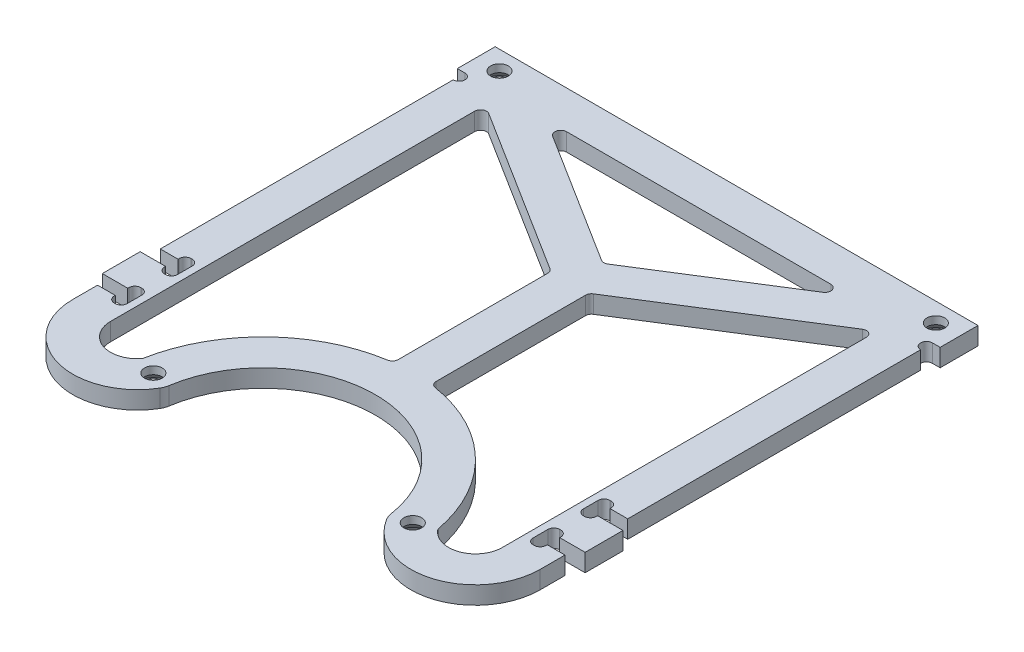
SolidWorks part; units mm, degrees
ref_plane "Front Plane" through (0, 0, 0) normal (0, 0, 1) x (1, 0, 0)
ref_plane "Top Plane" through (0, 0, 0) normal (0, 1, 0) x (1, 0, 0)
ref_plane "Right Plane" through (0, 0, 0) normal (1, 0, 0) x (0, 0, -1)
sketch "Sketch1" plane through (0, 0, 0) normal (0, 1, 0) x (1, 0, 0)
  line L0 (-36.88, 36.725) -> (36.88, 36.725) construction
  line L1 (36.88, 36.725) -> (21.92, -36.725) construction
  line L2 (21.92, -36.725) -> (-21.92, -36.725) construction
  line L3 (-21.92, -36.725) -> (-36.88, 36.725) construction
  line L4 (0, -40.095) -> (0, -36.725) construction
  line L5 (0, 36.725) -> (0, -36.725) construction
  line L6 (-39.5, -13.775) -> (-39.5, 33.525)
  line L7 (-33.1, -13.775) -> (-33.1, 33.525)
  line L8 (-39.5, 9.875) -> (-33.1, 9.875) construction
  line L9 (0, 33.525) -> (0, 39.925) construction
  line L10 (-39.5, -23.275) -> (-33.1, -23.275) construction
  line L13 (40.8, 33.525) -> (-40.8, 33.525)
  line L14 (40.8, 33.525) -> (40.8, 39.925)
  line L15 (40.8, 39.925) -> (-40.8, 39.925)
  line L16 (-40.8, 33.525) -> (-40.8, 39.925)
  line L17 (40.8, 33.525) -> (-40.8, 39.925) construction
  line L18 (40.8, 39.925) -> (-40.8, 33.525) construction
  line L19 (39.5, 33.525) -> (-39.5, 33.525)
  line L20 (39.5, 33.525) -> (39.5, 39.925)
  line L21 (39.5, 39.925) -> (-39.5, 39.925)
  line L22 (-39.5, 33.525) -> (-39.5, 39.925)
  line L23 (39.5, 33.525) -> (-39.5, 39.925) construction
  line L24 (39.5, 39.925) -> (-39.5, 33.525) construction
  line L27 (-34.3, -25.275) -> (-36.5, -25.275)
  line L28 (-39.5, -20.075) -> (-40.8, -20.075)
  line L29 (-34.3, -16.775) -> (-34.3, -13.775) construction
  line L30 (-33.1, -32.775) -> (-39.5, -32.775)
  line L31 (-33.1, -32.775) -> (-33.1, -13.775)
  line L32 (-33.1, -13.775) -> (-39.5, -13.775)
  line L33 (-39.5, -32.775) -> (-39.5, -13.775)
  line L34 (-33.1, -32.775) -> (-39.5, -13.775) construction
  line L35 (-33.1, -13.775) -> (-39.5, -32.775) construction
  line L36 (-39.5, -20.075) -> (-36.5, -20.075)
  line L37 (-39.5, -20.075) -> (-39.5, -17.975)
  line L38 (-39.5, -17.975) -> (-36.5, -17.975)
  line L39 (-36.5, -20.075) -> (-36.5, -17.975)
  line L40 (-36.5, -19.025) -> (-39.5, -19.025) construction
  line L41 (-36.5, -19.025) -> (-33.1, -19.025) construction
  line L42 (-35.4, -32.775) -> (-35.4, -13.775) construction
  line L43 (-34.3, -21.275) -> (-36.5, -21.275)
  line L44 (-34.3, -21.275) -> (-34.3, -16.775)
  line L45 (-34.3, -16.775) -> (-36.5, -16.775)
  line L46 (-36.5, -21.275) -> (-36.5, -16.775)
  line L47 (-34.3, -21.275) -> (-36.5, -16.775) construction
  line L48 (-34.3, -16.775) -> (-36.5, -21.275) construction
  line L53 (-34.3, -25.275) -> (-34.3, -29.775)
  line L58 (-34.3, -29.775) -> (-36.5, -29.775)
  line L67 (39.5, -17.975) -> (36.5, -17.975)
  line L68 (-36.5, -25.275) -> (-36.5, -29.775)
  line L69 (-39.5, -28.575) -> (-36.5, -28.575)
  line L70 (-39.5, -20.075) -> (-39.5, -26.475)
  line L71 (-39.5, -26.475) -> (-40.8, -26.475)
  line L72 (-40.8, -20.075) -> (-40.8, -26.475)
  line L73 (-39.5, -20.075) -> (-40.8, -26.475) construction
  line L74 (-39.5, -26.475) -> (-40.8, -20.075) construction
  line L75 (-39.5, -26.475) -> (-36.5, -26.475)
  line L76 (39.5, -20.075) -> (36.5, -20.075)
  line L77 (39.5, -28.575) -> (36.5, -28.575)
  line L78 (39.5, -26.475) -> (36.5, -26.475)
  line L79 (36.5, -25.275) -> (36.5, -29.775)
  line L80 (34.3, -29.775) -> (36.5, -29.775)
  line L81 (34.3, -25.275) -> (34.3, -29.775)
  line L82 (34.3, -25.275) -> (36.5, -25.275)
  line L83 (34.3, -21.275) -> (36.5, -21.275)
  line L84 (34.3, -21.275) -> (34.3, -16.775)
  line L85 (34.3, -16.775) -> (36.5, -16.775)
  line L86 (36.5, -21.275) -> (36.5, -16.775)
  line L87 (39.5, -17.975) -> (36.5, -17.975)
  line L88 (39.5, -20.075) -> (40.8, -20.075)
  line L89 (40.8, -20.075) -> (40.8, -26.475)
  line L90 (39.5, -26.475) -> (40.8, -26.475)
  line L91 (39.5, -32.775) -> (39.5, -13.775)
  line L92 (33.1, -32.775) -> (33.1, -13.775)
  line L93 (33.1, -13.775) -> (33.1, 33.525)
  line L94 (39.5, -13.775) -> (39.5, 33.525)
  line L95 (-36.88, 36.725) -> (0, 13.525) construction
  line L96 (0, 13.525) -> (36.88, 36.725) construction
  line L97 (-38.5839, 34.0164) -> (-1.7039, 10.8164)
  line L98 (-38.5839, 34.0164) -> (-35.1761, 39.4336)
  line L99 (-1.7039, 10.8164) -> (1.7039, 16.2336)
  line L100 (-35.1761, 39.4336) -> (1.7039, 16.2336)
  line L101 (-38.5839, 34.0164) -> (1.7039, 16.2336) construction
  line L102 (-1.7039, 10.8164) -> (-35.1761, 39.4336) construction
  line L103 (1.7039, 10.8164) -> (-1.7039, 16.2336)
  line L104 (35.1761, 39.4336) -> (-1.7039, 16.2336)
  line L105 (38.5839, 34.0164) -> (35.1761, 39.4336)
  line L106 (38.5839, 34.0164) -> (1.7039, 10.8164)
  line L108 (-3.2, 13.525) -> (3.2, 13.525)
  line L109 (-3.2, 13.525) -> (-3.2, -14.92)
  line L110 (-3.2, -14.92) -> (3.2, -14.92)
  line L111 (3.2, 13.525) -> (3.2, -14.92)
  circle A0 centre (21.92, -36.725) radius 1.5
  circle A1 centre (-21.92, -36.725) radius 1.5
  circle A2 centre (-36.88, 36.725) radius 1.5
  circle A3 centre (36.88, 36.725) radius 1.5
  circle A4 centre (-36.88, 36.725) radius 3.2
  circle A5 centre (-21.92, -36.725) radius 3.2
  circle A6 centre (21.92, -36.725) radius 3.2
  circle A7 centre (36.88, 36.725) radius 3.2
  circle A8 centre (0, -40.095) radius 16
  circle A9 centre (0, -40.095) radius 25.3775
  circle A10 centre (0, -40.095) radius 18.9775
  arc A11 (-39.5, -32.775) -> (-19.169, -38.3597) centre (-28.5675, -32.775) ccw
  arc A12 (-33.1, -32.775) -> (-24.671, -35.0903) centre (-28.5675, -32.775) ccw
  arc A13 (33.1, -32.775) -> (24.671, -35.0903) centre (28.5675, -32.775) cw
  arc A14 (39.5, -32.775) -> (19.169, -38.3597) centre (28.5675, -32.775) cw
  circle A15 centre (-39.5, 32.525) radius 1
  circle A16 centre (39.5, 32.525) radius 1
  circle A17 centre (0, 13.525) radius 3.2
  point P10 (0, 0)
  point P26 (0, -23.275)
  point P29 (-40.15, -23.275)
  point P37 (-36.3, -23.275)
  point P53 (-35.4, -19.025)
  point P101 (0, 0)
  point P104 (-18.44, 25.125)
  point P105 (0, 0)
  dimension "D4" = 3
  dimension "D5" = 6.4
  dimension "D6" = 32
  dimension "D11" = 2
  dimension "D1" = 74.958
  dimension "D2" = 43.84
  dimension "D3" = 73.76
  dimension "D7" = 3.37
  dimension "D8" = 81.6
  dimension "D9" = 60
  dimension "D10" = 79
  dimension "D12" = 2.1
  dimension "D13" = 2.2
  dimension "D14" = 4.5
  dimension "D15" = 3
  dimension "D16" = 20
extrude "Shape" add sketch "Sketch1" along normal blind 3 contours A15 L6 L32 L7 L97 L19 | L106 L19 L13 L93 | A17 L111 L106 L93 L19 L104 L100 | A17 L104 L100 L13 L7 L97 L109 | L13 L19 L97 L7 | A17 L109 L97 | A17 L106 L111 | A17 L97 L109 A9 L111 L106 | A13 A9 L110 A12 A5 A10 A6 | A9 A11 A5 | A12 L30 A11 A9 | A14 A9 A6 | L94 A16 L13 L106 L93 L92 A13 A9 A14 L91 L77 L79 L80 L81 L82 L78 L76 L86 L83 L84 L85 L67 | L33 L75 L68 L27 L53 L58 L69 L30 L31 L32 L38 L46 L45 L44 L43 L36 | L28 L72 L71 L33 | A5 A1 | A6 A0 | L91 L90 L89 L88 | L99 A17 L103 | L103 A17 L108 | L108 A17 L99 | L99 A17 L103 | L103 A17 L108 | L108 A17 L99 | A17 L100 L104 | A12 A9 A5 | A9 A13 A6 | A4 L22 L15 L16 L13 | L22 A4 | A4 L21 L22 | A4 L22 L19 L97 | L98 A4 L22 A2 | A4 L98 A2 | A4 L13 L100 | A7 L21 A4 L100 L13 L104 | A7 L20 L13 L14 L15 | L20 A7 | L105 A7 L20 A3 | A7 L20 L15 | A7 L106 L13 L20 | A7 L105 A3 | A7 L104 L19 L13 | A7 L19 L106 | A4 L97 L19 | L110 A9 region at (-36.3238, 0, -9.2182) region at (-36.2596, 0, 23.275) region at (-38.9631, 0, -33.9356) region at (-40.2377, 0, -36.725) region at (-34.6676, 0, -32.5389) region at (-16.6637, 0, -23.9048) region at (-32.2554, 0, 38.4576) region at (-40.15, 0, 23.275) region at (-37.7741, 0, -33.6246) region at (-39.7339, 0, -36.725) region at (-39.4268, 0, -36.725) region at (-31.4421, 0, -35.1569) region at (-2.8872, 0, -11.9303) region at (0, 0, 1.9589) region at (-24.9288, 0, 35.5908) region at (-17.0707, 0, 22.0628) region at (-35.5584, 0, -35.8937) region at (-38.8761, 0, -39.5371) region at (0, 0, -36.9019) region at (-1.7892, 0, -12.5368) region at (0, 0, -11.502) region at (-1.7892, 0, -14.5132) region at (0, 0, 14.839) region at (-23.615, 0, 40.6433) region at (-24.8469, 0, 35.6753) region at (31.4421, 0, -35.1569) region at (16.6637, 0, -23.9048) region at (0, 0, -16.8524) region at (0, 0, -15.548) region at (1.7892, 0, -12.5368) region at (1.7892, 0, -14.5132) region at (2.8872, 0, -11.9303) region at (23.615, 0, 40.6433) region at (35.4725, 0, 6.6194) region at (38.8761, 0, -39.5371) region at (38.3228, 0, -39.499) region at (34.6676, 0, -32.5389) region at (35.5584, 0, -35.8937) region at (24.9288, 0, 35.5908) region at (18.9931, 0, 37.7747) region at (40.2377, 0, -36.725) region at (39.7339, 0, -36.725) region at (37.7741, 0, -33.6246) region at (38.9631, 0, -33.9356) region at (40.15, 0, 23.275)
fillet "Mill fillets" radius 1 25 edges at (36.5, 1.5, 21.275) (34.3, 1.5, 21.275) (34.3, 1.5, 16.775) (36.5, 1.5, 16.775) (36.5, 1.5, 25.275) (34.3, 1.5, 25.275) (36.5, 1.5, 29.775) (34.3, 1.5, 29.775) (-36.5, 1.5, 21.275) (-34.3, 1.5, 21.275) (-34.3, 1.5, 16.775) (-36.5, 1.5, 16.775) (-36.5, 1.5, 25.275) (-34.3, 1.5, 25.275) (-34.3, 1.5, 29.775) (-36.5, 1.5, 29.775) (3.2, 1.5, 14.92) (-3.2, 1.5, 14.92) (-33.1, 1.5, -30.5666) (-3.2, 1.5, -11.7575) (3.2, 1.5, -11.7575) (33.1, 1.5, -30.5666) (0, 1.5, -17.3055) (25.7834, 1.5, -33.525) (-25.7834, 1.5, -33.525)
hole_wizard "M3 countersunks" positions "Sketch2" profile "Sketch3" countersink size "M3" standard "ANSI Metric" end condition through all
sketch "Sketch2" plane through (0, 0, 0) normal (0, -1, 0) x (-1, 0, 0)
  point P0 (21.92, -36.725)
  point P3 (-21.92, -36.725)
  point P6 (-36.88, 36.725)
  point P9 (36.88, 36.725)
sketch "Sketch3" plane through (-21.92, 0, 36.725) normal (1, 0, 0) x (0, 0, -1)
  line L0 (0, 0) -> (0, 3)
  line L1 (0, 3) -> (1.5, 3)
  line L2 (1.5, 3) -> (1.5, 1.7)
  line L3 (1.5, 1.7) -> (3, 0.2)
  line L4 (3, 0.2) -> (3, 0)
  line L6 (3, 0) -> (0, 0)
  line L7 (-1.5, 1.7) -> (-3, 0.2) construction
  line L11 (0, -6.35) -> (0, 107.95) construction
  dimension "Thru Hole Dia." = 3
  dimension "Thru Hole Depth" = 3
  dimension "C'Sink Dia." = 6
  dimension "C'Sink Angle" = 90
  dimension "Head Clearance" = 0.2
sketch "Sketch4" plane through (-39.5, 0, 0) normal (-1, 0, 0) x (0, 0, 1)
  line L0 (17.975, 3) -> (20.075, 0) construction
  line L1 (28.575, 0) -> (26.475, 3) construction
  point P8 (19.025, 1.5)
  point P9 (27.525, 1.5)
ref_axis "Tap axis 1" through (-50.6169, 1.5, 19.025) along (1, 0, 0)
ref_axis "Tap axis 2" through (-50.8013, 1.5, 27.525) along (1, 0, 0)
